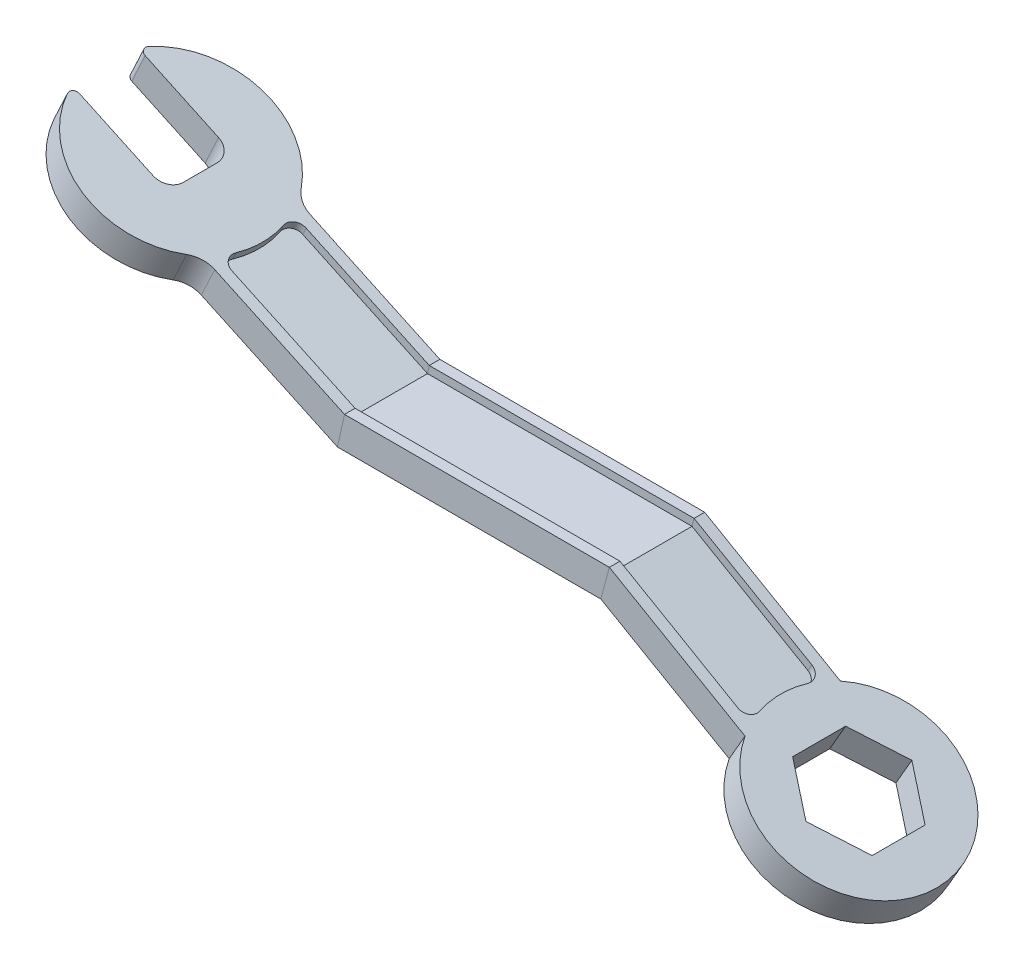
SolidWorks part; units mm, degrees
ref_plane "前视基准面" through (0, 0, 0) normal (0, 0, 1) x (1, 0, 0)
ref_plane "上视基准面" through (0, 0, 0) normal (0, 1, 0) x (1, 0, 0)
ref_plane "右视基准面" through (0, 0, 0) normal (1, 0, 0) x (0, 0, -1)
other "Configuration Table"
sketch "草图1" plane through (0, 0, 0) normal (0, 0, 1) x (1, 0, 0)
  line L0 (0, 0) -> (50, 0)
  line L1 (0, 0) -> (-19.9388, 9.2976)
  line L2 (50, 0) -> (69.0526, -11)
  dimension "D1" = 50
  dimension "D2" = 22
  dimension "D3" = 22
  dimension "D4" = 25
  dimension "D5" = 30
sketch "草图2" plane through (0, 0, 0) normal (1, 0, 0) x (0, 0, -1)
  line L0 (0, 0) -> (9, -3) construction
  line L1 (0, 0) -> (2, 0)
  line L2 (0, 0) -> (0, -6)
  line L3 (0, -6) -> (2, -6)
  line L4 (18, 0) -> (18, -6)
  line L5 (18, 0) -> (9, -3) construction
  line L6 (2, -6) -> (2, -4.5)
  line L7 (2, -4.5) -> (16, -4.5)
  line L9 (2, -1.5) -> (16, -1.5)
  line L11 (9, -3) -> (16, -1.5) construction
  line L12 (2, -1.5) -> (9, -3) construction
  line L13 (16, -6) -> (16, -4.5)
  line L14 (16, 0) -> (18, 0)
  line L15 (16, -6) -> (18, -6)
  line L16 (2, -1.5) -> (2, 0)
  line L17 (4.5, -4.5) -> (0, -6) construction
  line L18 (13.5, -4.5) -> (18, -6) construction
  line L19 (16, -1.5) -> (16, 0)
  point P5 (9, -3)
  dimension "D1" = 18
  dimension "D2" = 6
  dimension "D3" = 14
  dimension "D4" = 3
sweep "扫描2" add profiles "草图2" path "草图1"
sketch "草图3" plane through (-0.6339, -1.3595, 0) normal (0.4226, 0.9063, 0) x (0.9063, -0.4226, 0)
  line L0 (-27, 9) -> (-44, 9) construction
  line L1 (-22, 16) -> (-22, 2) construction
  line L2 (-22, 9) -> (-22, 18.0192)
  line L3 (-22, 18.0192) -> (-29.5898, 18.0192)
  line L4 (-22, 9) -> (-22, 0)
  line L5 (-22, 0) -> (-29.5778, 0)
  line L6 (-40, 9) -> (-40, 15.2)
  line L7 (-40, 9) -> (-40, 2.8)
  line L8 (-40, 15.2) -> (-59.8291, 15.2)
  line L9 (-40, 2.8) -> (-59.8291, 2.8)
  arc A0 (-29.5898, 18.0192) -> (-59.8291, 15.2) centre (-44, 9) ccw
  arc A1 (-59.8291, 2.8) -> (-29.5778, 0) centre (-44, 9) ccw
  dimension "D2" = 34
  dimension "D1" = 22
  dimension "D3" = 6.2
  dimension "D4" = 6.2
  dimension "D5" = 4
extrude "凸台-拉伸1" add sketch "草图3" against normal blind 6 from offset 1.5 contours A0 L8 L6 L7 L9 A1 L5 L4 L2 L3
fillet "圆角1" radius 1 2 edges at (-55.4914, 22.5659, -2.8) (-55.4914, 22.5659, -15.2)
fillet "圆角2" radius 5 2 edges at (-28.0744, 9.7812, 0) (-28.0853, 9.7863, -18.0192)
fillet "圆角3" radius 3 2 edges at (-37.5202, 14.1858, -2.8) (-37.5202, 14.1858, -15.2)
sketch "草图4" plane through (0, 0, 0) normal (0.4226, 0.9063, 0) x (0.9063, -0.4226, 0)
  line L0 (-22, 16) -> (-28.5081, 16)
  line L1 (-22, 2) -> (-28.5081, 2)
  line L2 (-22, 16) -> (-22, 2)
  arc A0 (-28.5081, 2) -> (-28.5081, 16) centre (-44, 9) ccw
extrude "切除-拉伸1" cut sketch "草图4" against normal blind 1.5
fillet "圆角4" radius 2 2 edges at (-26.154, 11.3683, -2) (-26.154, 11.3683, -16)
extrude "切除-拉伸2" cut sketch "草图4<2>" against normal blind 1.5 from offset 4.5 contours L2 L1 A0 L0 offset against normal yes
sketch "草图4<2>" plane through (0, 0, 0) normal (0.4226, 0.9063, 0) x (0.9063, -0.4226, 0) same geometry as "草图4"
fillet "圆角5" radius 2 2 edges at (-28.0558, 7.2899, -16) (-28.0558, 7.2899, -2)
ref_plane "基准面1" through (69.0526, -11, -18) normal (0.866, -0.5, 0) x (0, 0, -1)
sketch "草图7" plane through (12.5, 21.6506, 0) normal (0.5, 0.866, 0) x (0.866, -0.5, 0)
  line L0 (65.3013, 9) -> (70.3013, 9) construction
  line L1 (65.3013, 16) -> (65.3013, 2) construction
  line L2 (65.3013, 18) -> (72.8791, 18)
  line L3 (87.3013, 19) -> (78.641, 14)
  line L4 (78.641, 14) -> (78.641, 4)
  line L5 (78.641, 4) -> (87.3013, -1)
  line L6 (87.3013, -1) -> (95.9615, 4)
  line L7 (95.9615, 4) -> (95.9615, 14)
  line L8 (95.9615, 14) -> (87.3013, 19)
  line L9 (65.3013, 0) -> (72.8791, 0)
  line L10 (78.641, 9) -> (87.3013, 9) construction
  line L11 (65.3013, 18) -> (65.3013, -0.3497)
  arc A0 (72.8791, 0) -> (72.8791, 18) centre (87.3013, 9) ccw
  circle A1 centre (87.3013, 9) radius 8.6603 construction
  line M4 (65.3013, 16) -> (65.3013, 18)
  dimension "D2" = 34
  dimension "D1" = 22
  dimension "D3" = 20
extrude "凸台-拉伸2" add sketch "草图7" against normal blind 6 contours L9 A0 L2 L11 L8 L7 L6 L5 L4 L3 M4 | L9 A0 L2 L11 region at (72.3338, -12.8944, -17.4826)
sketch "草图8" plane through (12.5, 21.6506, 0) normal (0.5, 0.866, 0) x (0.866, -0.5, 0)
  line L0 (65.3013, 16) -> (65.3013, 2)
  line L1 (65.3013, 2) -> (71.8093, 2)
  line L2 (65.3013, 16) -> (71.8093, 16)
  arc A0 (71.8093, 16) -> (71.8093, 2) centre (87.3013, 9) ccw
extrude "切除-拉伸3" cut sketch "草图8" against normal blind 1.5
fillet "圆角6" radius 2 2 edges at (74.3137, -14.9036, -2) (74.3137, -14.9036, -16)
extrude "切除-拉伸4" cut sketch "草图8<2>" against normal blind 1.5 from offset 4.5 contours L0 L1 A0 L2 offset against normal yes
sketch "草图8<2>" plane through (12.5, 21.6506, 0) normal (0.5, 0.866, 0) x (0.866, -0.5, 0) same geometry as "草图8"
fillet "圆角7" radius 2 2 edges at (72.0637, -18.8007, -16) (72.0637, -18.8007, -2)
